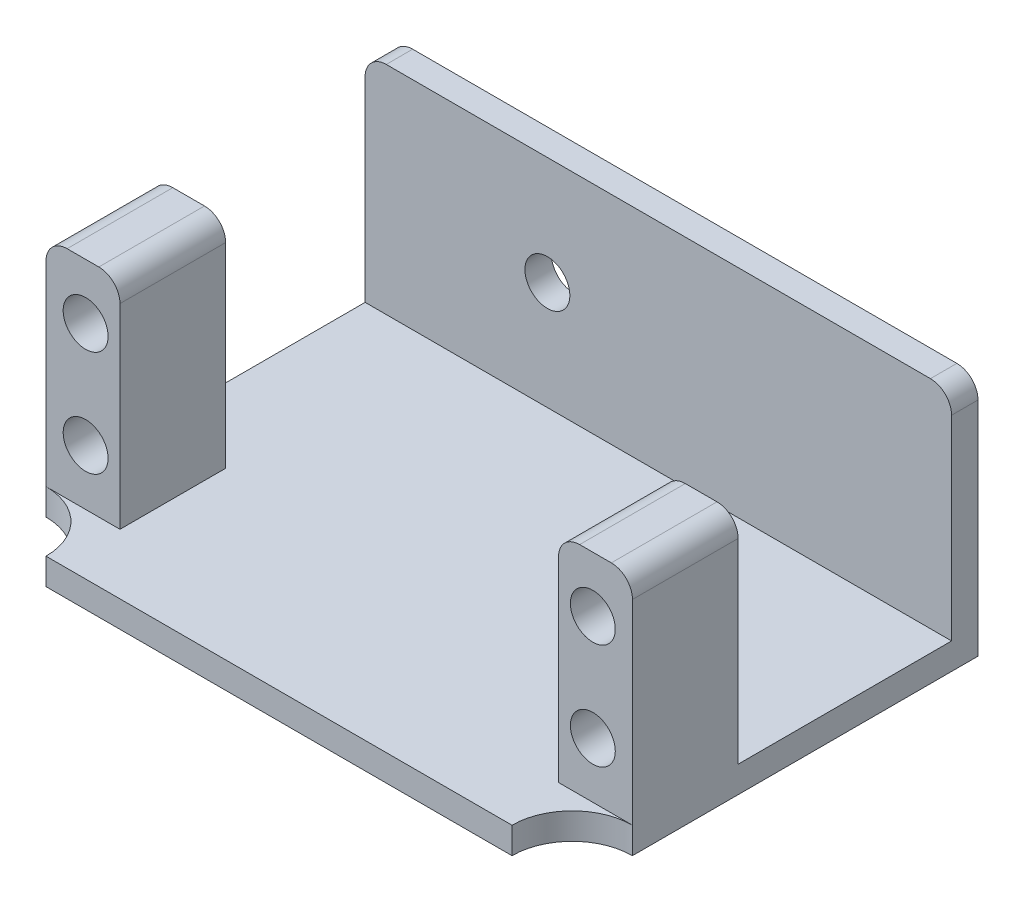
SolidWorks part; units mm, degrees
ref_plane "Front" through (0, 0, 0) normal (0, 0, 1) x (1, 0, 0)
ref_plane "Top" through (0, 0, 0) normal (0, 1, 0) x (1, 0, 0)
ref_plane "Right" through (0, 0, 0) normal (1, 0, 0) x (0, 0, -1)
sketch "Sketch1" plane through (0, 0, 0) normal (0, 1, 0) x (1, 0, 0)
  line L1 (0, 0) -> (55.5, 0)
  line L2 (0, 0) -> (0, 35.9)
  line L3 (0, 35.9) -> (55.5, 35.9)
  line L4 (55.5, 0) -> (55.5, 35.9)
  dimension "D1" = 35.9
  dimension "D2" = 55.5
extrude "bracketBase" add sketch "Sketch1" along normal blind 2.5
ref_plane "referencePlane1" through (0, 0, -8.2) normal (0, 0, 1) x (1, 0, 0)
sketch "Sketch2" plane through (0, 0, -8.2) normal (0, 0, 1) x (1, 0, 0)
  line L0 (27.75, 2.5) -> (27.75, 23) construction
  line L1 (0, 2.5) -> (7, 2.5)
  line L2 (0, 2.5) -> (0, 23)
  line L3 (0, 23) -> (7, 23)
  line L4 (7, 2.5) -> (7, 23)
  line L5 (0, 2.5) -> (55.5, 2.5) construction
  line L6 (55.5, 23) -> (48.5, 23)
  line L7 (48.5, 2.5) -> (48.5, 23)
  line L8 (55.5, 2.5) -> (48.5, 2.5)
  line L9 (55.5, 2.5) -> (55.5, 23)
  dimension "D1" = 20.5
  dimension "D2" = 7
extrude "servoMountingHoleTabs" add sketch "Sketch2" along normal blind 2.5
sketch "Sketch3" plane through (0, 0, -5.7) normal (0, 0, 1) x (1, 0, 0)
  line L0 (0, 12.75) -> (7, 12.75) construction
  line L3 (0, 23) -> (0, 2.5) construction
  line L4 (7, 2.5) -> (7, 23) construction
  line L5 (7, 23) -> (0, 23) construction
  line L6 (27.75, 2.5) -> (27.75, 23) construction
  line L7 (0, 2.5) -> (55.5, 2.5) construction
  circle A0 centre (3.75, 17.75) radius 2.125
  circle A1 centre (3.75, 7.75) radius 2.125
  circle A2 centre (51.75, 7.75) radius 2.125
  circle A3 centre (51.75, 17.75) radius 2.125
  dimension "D1" = 4.25
  dimension "D2" = 3.75
  dimension "D3" = 5.25
extrude "servoMountingHoles" cut sketch "Sketch3" against normal blind 2.5
sketch "Sketch4" plane through (0, 0, 0) normal (0, 1, 0) x (1, 0, 0)
  line L0 (55.5, 8.2) -> (55.5, 35.9) construction
  line L1 (0, 35.9) -> (55.5, 35.9)
  line L2 (0, 35.9) -> (0, 38.4)
  line L3 (0, 38.4) -> (55.5, 38.4)
  line L4 (55.5, 35.9) -> (55.5, 38.4)
  dimension "D1" = 2.5
extrude "baseWall" add sketch "Sketch4" along normal up to surface (23 mm away) up to face at (3.5, 23, -6.95)
sketch "Sketch6" plane through (0, 2.5, 0) normal (0, 1, 0) x (1, 0, 0)
  circle A0 centre (0, 0) radius 5.7
  circle A1 centre (55.5, 0) radius 5.7
extrude "baseTrim" cut sketch "Sketch6" against normal blind 2.5
fillet "Fillet1" radius 2 6 edges at (7, 23, -6.95) (48.5, 23, -6.95) (0, 23, -6.95) (55.5, 23, -6.95) (55.5, 23, -37.15) (0, 23, -37.15)
sketch "Sketch7" plane through (0, 0, -38.4) normal (0, 0, -1) x (-1, 0, 0)
  line L0 (0, 21) -> (0, 0) construction
  line L1 (-55.5, 0) -> (0, 0) construction
  circle A0 centre (-17.25, 12.75) radius 2.125
  dimension "D1" = 4.25
  dimension "D2" = 17.25
  dimension "D3" = 12.75
extrude "M4mountingHole" cut sketch "Sketch7" against normal blind 10
sketch "Sketch8" plane through (0, 0, -8.2) normal (0, 0, -1) x (-1, 0, 0)
  line L4 (-48.5, 2.5) -> (-48.5, 21)
  line L5 (-50.5, 23) -> (-53.5, 23)
  line L6 (-55.5, 21) -> (-55.5, 2.5)
  line L7 (-55.5, 2.5) -> (-48.5, 2.5)
  line L8 (-48.5, 2.5) -> (-48.5, 21)
  line L9 (-50.5, 23) -> (-53.5, 23)
  line L10 (-55.5, 21) -> (-55.5, 2.5)
  line L11 (-55.5, 2.5) -> (-48.5, 2.5)
  line L12 (-2, 23) -> (-5, 23)
  line L13 (-7, 21) -> (-7, 2.5)
  line L14 (-7, 2.5) -> (0, 2.5)
  line L15 (0, 2.5) -> (0, 21)
  line L16 (-2, 23) -> (-5, 23)
  line L17 (-7, 21) -> (-7, 2.5)
  line L18 (-7, 2.5) -> (0, 2.5)
  line L19 (0, 2.5) -> (0, 21)
  circle A0 centre (-51.75, 17.75) radius 2.125 construction
  circle A1 centre (-51.75, 17.75) radius 2.125
  arc A2 (-48.5, 21) -> (-50.5, 23) centre (-50.5, 21) ccw
  arc A3 (-53.5, 23) -> (-55.5, 21) centre (-53.5, 21) ccw
  arc A4 (-48.5, 21) -> (-50.5, 23) centre (-50.5, 21) ccw
  arc A5 (-53.5, 23) -> (-55.5, 21) centre (-53.5, 21) ccw
  arc A6 (-5, 23) -> (-7, 21) centre (-5, 21) ccw
  arc A7 (0, 21) -> (-2, 23) centre (-2, 21) ccw
  arc A8 (-5, 23) -> (-7, 21) centre (-5, 21) ccw
  arc A9 (0, 21) -> (-2, 23) centre (-2, 21) ccw
  circle A10 centre (-51.75, 7.75) radius 2.125 construction
  circle A11 centre (-51.75, 7.75) radius 2.125
  circle A12 centre (-3.75, 17.75) radius 2.125 construction
  circle A13 centre (-3.75, 17.75) radius 2.125
  circle A14 centre (-3.75, 7.75) radius 2.125 construction
  circle A15 centre (-3.75, 7.75) radius 2.125
  dimension "D1" = 0
  dimension "D2" = 0
extrude "Boss-Extrude1" add sketch "Sketch8" along normal blind 7.5
